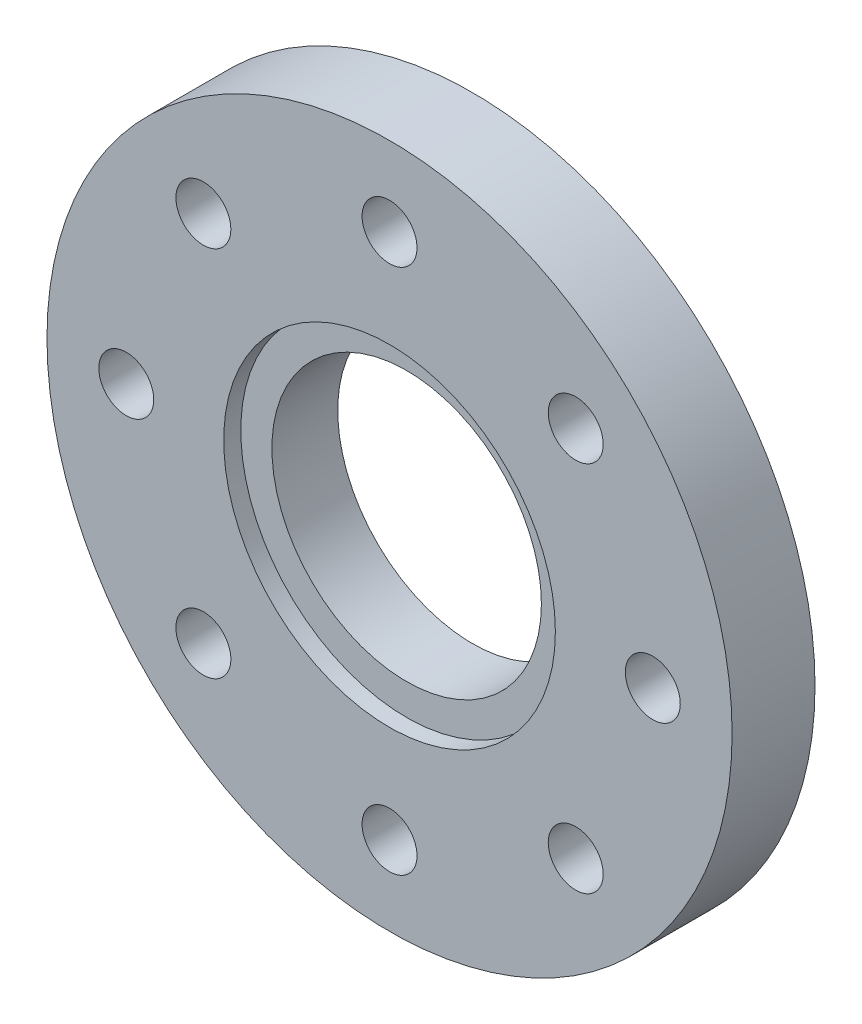
SolidWorks part; units mm, degrees
other "Markup1"
sketch "Sketch6" plane through (33.05, -33.05, -8) normal (0.0959, -0.0026, -0.9954) x (-0.8845, 0.4584, -0.0865)
other "Markup2"
sketch "Sketch7" plane through (33.05, -33.05, -8) normal (0.0959, -0.0026, -0.9954) x (-0.8845, 0.4584, -0.0865)
ref_plane "Front Plane" through (0, 0, 0) normal (0, 0, 1) x (1, 0, 0)
ref_plane "Top Plane" through (0, 0, 0) normal (0, 1, 0) x (1, 0, 0)
ref_plane "Right Plane" through (0, 0, 0) normal (1, 0, 0) x (0, 0, -1)
sketch "Sketch1" plane through (0, 0, 0) normal (0, 0, 1) x (1, 0, 0)
  circle A0 centre (0, 0) radius 13
  circle A1 centre (0, 0) radius 16 construction
  circle A3 centre (0, 0) radius 33.05
  circle A4 centre (0, 0) radius 25.4 construction
  circle A8 centre (0, 0) radius 16
  circle A12 centre (0, 0) radius 33.05
  point P21 (0, 0)
  point P70 (0, 0)
  dimension "D1" = 26
  dimension "D2" = 32
  dimension "D3" = 7.65
  dimension "D5" = 50.8
extrude "Boss-Extrude1" add sketch "Sketch1" against normal blind 8 contours A8 A0 | A8 region at (-32.1152, 0, 0) region at (-15.5475, 0, 0)
extrude "Cut-Extrude1" cut sketch "Sketch1<10>" against normal blind 1.65 contours A8 A0 region at (-15.5475, 0, 0)
sketch "Sketch1<10>" plane through (0, 0, 0) normal (0, 0, 1) x (1, 0, 0) same geometry as "Sketch1"
sketch "Sketch8" plane through (0, 0, -8) normal (0, 0, -1) x (-1, 0, 0)
  line L1 (2.4826, 21.1) -> (4.9652, 25.4)
  line L2 (4.9652, 25.4) -> (2.4826, 29.7)
  line L3 (2.4826, 29.7) -> (-2.4826, 29.7)
  line L4 (-2.4826, 29.7) -> (-4.9652, 25.4)
  line L5 (-4.9652, 25.4) -> (-2.4826, 21.1)
  line L6 (-2.4826, 21.1) -> (2.4826, 21.1)
  circle A0 centre (-59.8961, -78.4521) radius 27.9 construction
  circle A1 centre (0, 25.4) radius 4.3 construction
  circle A2 centre (0, 0) radius 25.4 construction
  circle B0 centre (-59.8961, -103.8521) radius 2.5
  circle B1 centre (-77.8566, -96.4126) radius 2.5
  circle B2 centre (-85.2961, -78.4521) radius 2.5
  circle B3 centre (-77.8566, -60.4916) radius 2.5
  circle B4 centre (-59.8961, -53.0521) radius 2.5
  circle B5 centre (-41.9356, -60.4916) radius 2.5
  circle B6 centre (-34.4961, -78.4521) radius 2.5
  circle B7 centre (-41.9356, -96.4126) radius 2.5
  dimension "D1" = 8.6
sketch_block_instance "bearing_house_holes-1"
sketch_block "bearing_house_holes"
extrude "Cut-Extrude2" cut sketch "Sketch8" against normal blind 4.1
sketch "Sketch9" plane through (0, 0, -8) normal (0, 0, -1) x (-1, 0, 0)
  circle A0 centre (0, 25.4) radius 2.65
  circle A1 centre (0, 0) radius 25.4 construction
  dimension "D1" = 5.3
extrude "Cut-Extrude3" cut sketch "Sketch9" against normal blind 8 contours A0
pattern_circular "CirPattern1" count 8 every 45 about axis through (0, 0, -8) along (0, 0, 1) of "Cut-Extrude2", "Cut-Extrude3"
